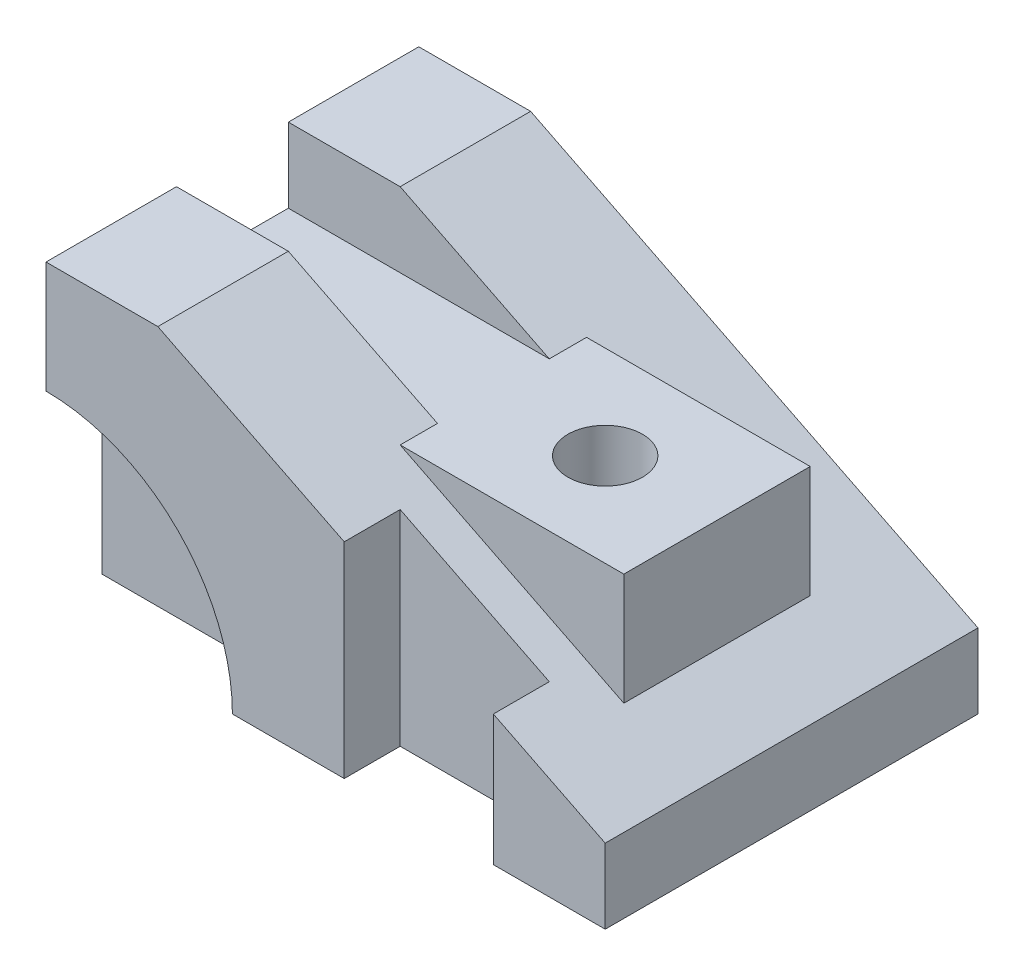
SolidWorks part; units mm, degrees
ref_plane "Front Plane" through (0, 0, 0) normal (0, 0, 1) x (1, 0, 0)
ref_plane "Top Plane" through (0, 0, 0) normal (0, 1, 0) x (1, 0, 0)
ref_plane "Right Plane" through (0, 0, 0) normal (1, 0, 0) x (0, 0, -1)
sketch "Sketch2" plane through (0, 0, 0) normal (0, 0, 1) x (1, 0, 0)
  line L0 (0, 0) -> (150, 0)
  line L1 (150, 0) -> (150, 20)
  line L2 (150, 20) -> (30, 80)
  line L3 (30, 80) -> (0, 80)
  line L4 (0, 80) -> (0, 0)
  dimension "D1" = 20
  dimension "D2" = 30
  dimension "D3" = 80
  dimension "D4" = 150
extrude "Boss-Extrude1" add sketch "Sketch2" against normal blind 50 and the other way blind 50
sketch "Sketch3" plane through (0, 0, 50) normal (0, 0, 1) x (1, 0, 0)
  circle A0 centre (0, 0) radius 50
  dimension "D1" = 100
extrude "Cut-Extrude1" cut sketch "Sketch3" against normal blind 15
sketch "Sketch6" plane through (0, 0, 0) normal (0, 0, 1) x (1, 0, 0)
  line L0 (70, 60) -> (130, 60)
  line L1 (150, 20) -> (30, 80) construction
  line L2 (130, 60) -> (130, 30)
  line L3 (130, 30) -> (70, 60)
  line L4 (150, 0) -> (150, 20) construction
  dimension "D1" = 20
  dimension "D2" = 30
extrude "Boss-Extrude2" add sketch "Sketch6" along normal blind 25 and the other way blind 25
sketch "Sketch7" plane through (0, 60, 0) normal (0, 1, 0) x (1, 0, 0)
  line L0 (30, 50) -> (0, 50) construction
  line L1 (-10.3476, 15) -> (94.381, 15)
  line L2 (-10.3476, 15) -> (-10.3476, -15)
  line L3 (-10.3476, -15) -> (94.381, -15)
  line L4 (94.381, 15) -> (94.381, -15)
  line L5 (30, -50) -> (0, -50) construction
  dimension "D1" = 35
  dimension "D2" = 35
extrude "Cut-Extrude2" cut sketch "Sketch7" along normal through all contours L1 L4 L3 L2
sketch "Sketch8" plane through (0, 60, 0) normal (0, 1, 0) x (1, 0, 0)
  line L0 (70, 25) -> (130, 25) construction
  line L2 (130, 25) -> (130, -25) construction
  circle A0 centre (100, 0) radius 10
  dimension "D1" = 20
  dimension "D2" = 25
  dimension "D3" = 30
extrude "Cut-Extrude3" cut sketch "Sketch8" against normal through all
sketch "Sketch9" plane through (0, 0, 0) normal (0, -1, 0) x (1, 0, 0)
  line L0 (50, 50) -> (150, 50) construction
  line L1 (80, 50) -> (120, 50)
  line L2 (80, 50) -> (80, 35)
  line L3 (80, 35) -> (120, 35)
  line L4 (120, 50) -> (120, 35)
  line L5 (150, 50) -> (150, -50) construction
  dimension "D1" = 15
  dimension "D2" = 40
  dimension "D3" = 30
extrude "Cut-Extrude4" cut sketch "Sketch9" against normal through all
